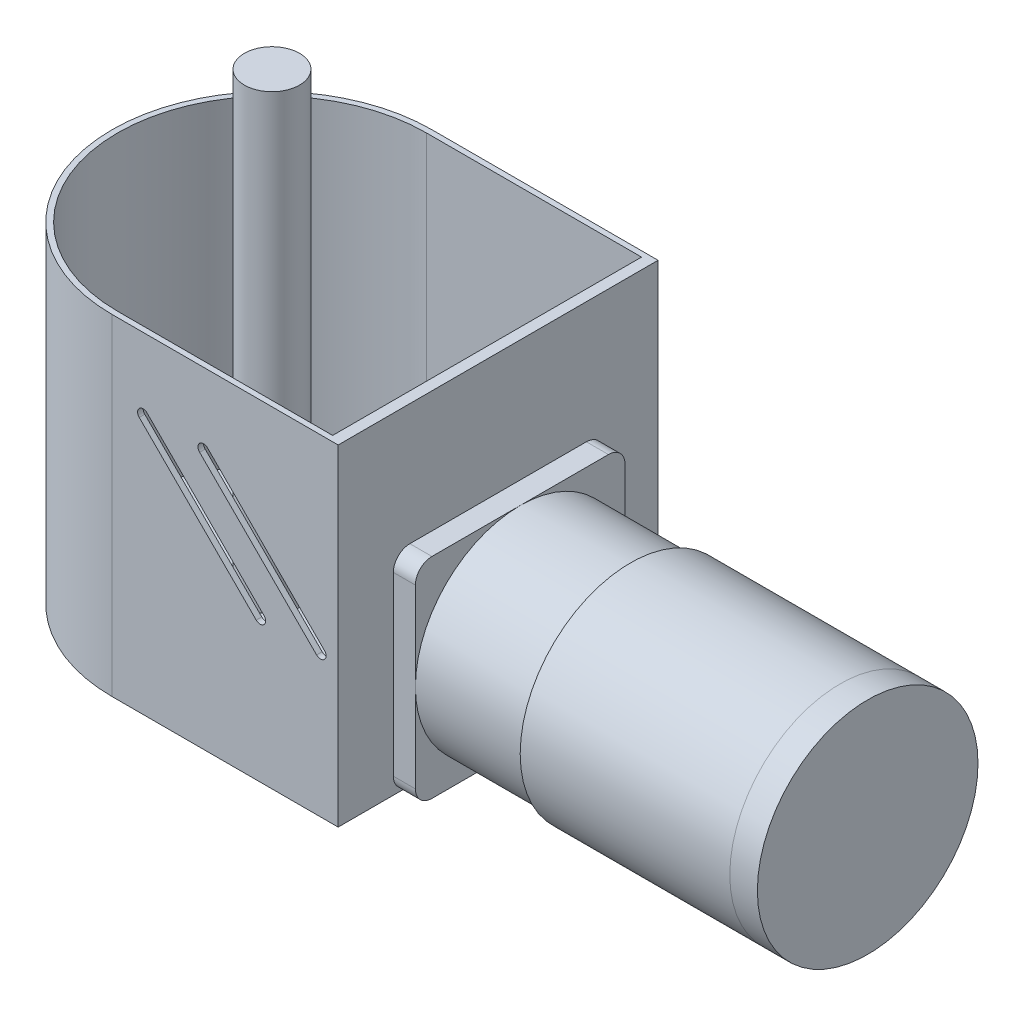
SolidWorks part; units mm, degrees
ref_plane "Front Plane" through (0, 0, 0) normal (0, 0, 1) x (1, 0, 0)
ref_plane "Top Plane" through (0, 0, 0) normal (0, 1, 0) x (1, 0, 0)
ref_plane "Right Plane" through (0, 0, 0) normal (1, 0, 0) x (0, 0, -1)
sketch "Sketch1" plane through (0, 0, 0) normal (0, 1, 0) x (1, 0, 0)
  line L1 (0, 0) -> (70, 0)
  line L2 (0, 0) -> (0, 58)
  line L3 (0, 58) -> (70, 58)
  line L4 (70, 0) -> (70, 58)
  dimension "D1" = 70
  dimension "D2" = 58
extrude "Boss-Extrude1" add sketch "Sketch1" along normal blind 60
fillet "Fillet2" radius 29 2 edges at (0, 30, 0) (0, 30, -58)
sketch "Sketch2" plane through (0, 60, 0) normal (0, 1, 0) x (1, 0, 0)
  line L0 (29, 57) -> (68, 57)
  line L1 (68, 57) -> (68, 1)
  line L2 (68, 1) -> (29, 1)
  line L3 (70, 0) -> (70, 58) construction
  arc A0 (29, 57) -> (29, 1) centre (29, 29) ccw
  dimension "D1" = 28
  dimension "D2" = 2
extrude "Cut-Extrude1" cut sketch "Sketch2" against normal blind 58
sketch "Sketch3" plane through (70, 0, 0) normal (1, 0, 0) x (0, 0, -1)
  line L0 (0, 60) -> (0, 0) construction
  line L6 (0, 0) -> (58, 0) construction
  line L7 (10, 0) -> (48, 0)
  line L8 (10, 0) -> (10, 38)
  line L9 (10, 38) -> (48, 38)
  line L10 (48, 0) -> (48, 38)
  dimension "D1" = 38
  dimension "D2" = 38
  dimension "D3" = 10
extrude "Boss-Extrude6" add sketch "Sketch3" along normal blind 4
fillet "Fillet4" radius 3 4 edges at (72, 0, -48) (72, 38, -48) (72, 38, -10) (72, 0, -10)
sketch "Sketch7" plane through (74, 0, 0) normal (1, 0, 0) x (0, 0, -1)
  circle A0 centre (29, 19) radius 19
extrude "Boss-Extrude7" add sketch "Sketch7" along normal blind 20
sketch "Sketch8" plane through (94, 0, 0) normal (1, 0, 0) x (0, 0, -1)
  circle A0 centre (29, 19) radius 20
  circle A1 centre (29, 19) radius 19 construction
  dimension "D1" = 1
extrude "Boss-Extrude8" add sketch "Sketch8" along normal blind 38
sketch "Sketch9" plane through (132, 0, 0) normal (1, 0, 0) x (0, 0, -1)
  circle A0 centre (29, 19) radius 20
extrude "Boss-Extrude9" add sketch "Sketch9" along normal blind 5 separate body
sketch "Sketch10" plane through (0, 0, 0) normal (0, 0, 1) x (1, 0, 0)
  line L0 (34.6398, 47) -> (55.853, 25.7868) construction
  line L1 (35.3469, 47.7071) -> (56.5601, 26.4939)
  line L2 (33.9327, 46.2929) -> (55.1459, 25.0797)
  line L3 (45.5919, 47) -> (66.8051, 25.7868) construction
  line L6 (70, 60) -> (70, 0) construction
  line L7 (29, 60) -> (70, 60) construction
  line L8 (46.299, 47.7071) -> (67.5122, 26.4939)
  line L9 (44.8848, 46.2929) -> (66.098, 25.0797)
  arc A0 (35.3469, 47.7071) -> (33.9327, 46.2929) centre (34.6398, 47) ccw
  arc A1 (55.1459, 25.0797) -> (56.5601, 26.4939) centre (55.853, 25.7868) ccw
  arc A4 (46.299, 47.7071) -> (44.8848, 46.2929) centre (45.5919, 47) ccw
  arc A5 (66.098, 25.0797) -> (67.5122, 26.4939) centre (66.8051, 25.7868) ccw
  point P2 (45.2464, 36.3934)
  point P9 (56.1985, 36.3934)
  point P18 (0, 0)
  point P19 (0, 0)
  dimension "D3" = 30
  dimension "D1" = 2
  dimension "D5" = 45
  dimension "D6" = 13
extrude "Cut-Extrude2" cut sketch "Sketch10" against normal blind 5
sketch "Sketch11" plane through (0, 2, 0) normal (0, 1, 0) x (1, 0, 0)
  circle A0 centre (29, 29) radius 5
  dimension "D1" = 10
extrude "Boss-Extrude10" add sketch "Sketch11" along normal blind 82
